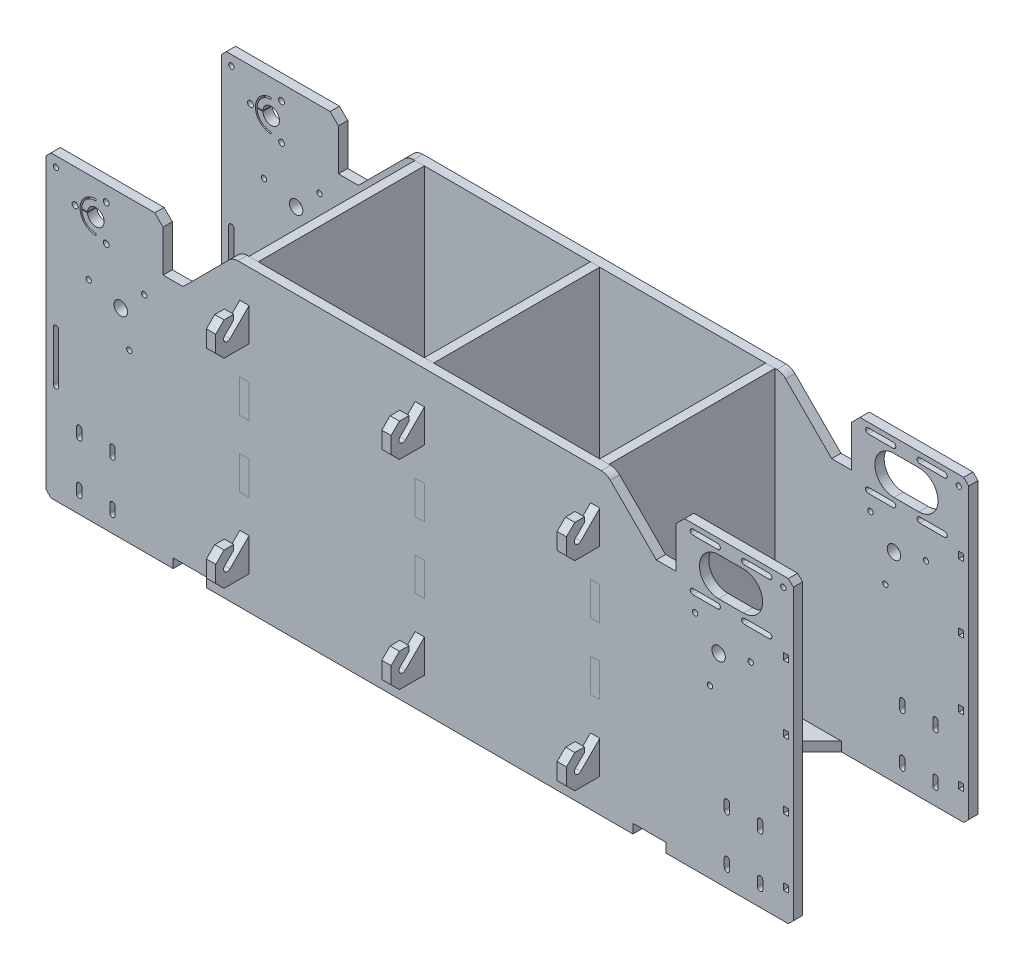
SolidWorks part; units mm, degrees
material "Perspex (TM) GS Acrylic Cast Sheet"
ref_plane "Front Plane" through (0, 0, 0) normal (0, 0, 1) x (1, 0, 0)
ref_plane "Top Plane" through (0, 0, 0) normal (0, 1, 0) x (1, 0, 0)
ref_plane "Right Plane" through (0, 0, 0) normal (1, 0, 0) x (0, 0, -1)
sketch "Sketch1" plane through (0, 0, 0) normal (0, 0, 1) x (1, 0, 0)
  line L0 (225, 180) -> (225, 0) construction
  line L1 (0, 0) -> (76.6, 0)
  line L2 (0, 0) -> (0, 180)
  line L4 (450, 0) -> (450, 180)
  line L5 (0, 90) -> (450, 90) construction
  line L6 (330.6, 180) -> (330.6, 0) construction
  line L7 (327.8, 160) -> (333.4, 160)
  line L8 (96.6, 0) -> (353.4, 0)
  line L12 (327.8, 160) -> (327.8, 140)
  line L13 (327.8, 140) -> (333.4, 140)
  line L14 (333.4, 160) -> (333.4, 140)
  line L15 (327.8, 120) -> (333.4, 120)
  line L16 (327.8, 120) -> (327.8, 100)
  line L17 (327.8, 100) -> (333.4, 100)
  line L18 (333.4, 120) -> (333.4, 100)
  line L19 (327.8, 80) -> (333.4, 80)
  line L20 (327.8, 80) -> (327.8, 60)
  line L21 (327.8, 60) -> (333.4, 60)
  line L22 (333.4, 80) -> (333.4, 60)
  line L23 (327.8, 40) -> (333.4, 40)
  line L24 (327.8, 40) -> (327.8, 20)
  line L25 (327.8, 20) -> (333.4, 20)
  line L26 (333.4, 40) -> (333.4, 20)
  line L27 (327.8, 40) -> (327.8, 20)
  line L28 (333.4, 40) -> (333.4, 20)
  line L29 (327.8, 80) -> (327.8, 60)
  line L30 (333.4, 80) -> (333.4, 60)
  line L31 (327.8, 120) -> (327.8, 100)
  line L32 (333.4, 120) -> (333.4, 100)
  line L33 (327.8, 160) -> (327.8, 140)
  line L34 (333.4, 160) -> (333.4, 140)
  line L39 (116.6, 160) -> (116.6, 140)
  line L40 (122.2, 160) -> (122.2, 140)
  line L41 (116.6, 120) -> (116.6, 100)
  line L42 (122.2, 120) -> (122.2, 100)
  line L43 (116.6, 80) -> (116.6, 60)
  line L44 (122.2, 80) -> (122.2, 60)
  line L45 (116.6, 40) -> (116.6, 20)
  line L46 (122.2, 40) -> (122.2, 20)
  line L47 (116.6, 40) -> (116.6, 20)
  line L48 (122.2, 20) -> (116.6, 20)
  line L49 (122.2, 40) -> (122.2, 20)
  line L50 (122.2, 40) -> (116.6, 40)
  line L51 (116.6, 80) -> (116.6, 60)
  line L52 (122.2, 60) -> (116.6, 60)
  line L53 (122.2, 80) -> (122.2, 60)
  line L54 (122.2, 80) -> (116.6, 80)
  line L55 (116.6, 120) -> (116.6, 100)
  line L56 (122.2, 100) -> (116.6, 100)
  line L57 (122.2, 120) -> (122.2, 100)
  line L58 (122.2, 120) -> (116.6, 120)
  line L59 (116.6, 160) -> (116.6, 140)
  line L60 (122.2, 140) -> (116.6, 140)
  line L61 (122.2, 160) -> (122.2, 140)
  line L66 (122.2, 160) -> (116.6, 160)
  line L67 (222.2, 160) -> (227.8, 160)
  line L72 (222.2, 160) -> (222.2, 140)
  line L73 (222.2, 140) -> (227.8, 140)
  line L74 (227.8, 160) -> (227.8, 140)
  line L75 (222.2, 120) -> (227.8, 120)
  line L76 (222.2, 120) -> (222.2, 100)
  line L77 (222.2, 100) -> (227.8, 100)
  line L78 (227.8, 120) -> (227.8, 100)
  line L79 (222.2, 80) -> (227.8, 80)
  line L80 (222.2, 80) -> (222.2, 60)
  line L81 (222.2, 60) -> (227.8, 60)
  line L82 (227.8, 80) -> (227.8, 60)
  line L83 (222.2, 40) -> (227.8, 40)
  line L84 (222.2, 40) -> (222.2, 20)
  line L85 (222.2, 20) -> (227.8, 20)
  line L86 (227.8, 40) -> (227.8, 20)
  line L88 (373.4, 0) -> (373.4, 5.6)
  line L89 (96.6, 0) -> (96.6, 5.6)
  line L90 (96.6, 5.6) -> (76.6, 5.6)
  line L91 (76.6, 0) -> (76.6, 5.6)
  line L92 (353.4, 5.6) -> (373.4, 5.6)
  line L93 (353.4, 0) -> (353.4, 5.6)
  line L94 (373.4, 0) -> (450, 0)
  line L95 (0, 180) -> (450, 180)
  point P1 (225, 160)
  point P2 (225, 120)
  point P9 (225, 80)
  point P11 (225, 40)
  point P12 (225, 180)
  dimension "D1" = 450
  dimension "D2" = 180
  dimension "D3" = 5.6
  dimension "D4" = 5.6
  dimension "D5" = 105.6
  dimension "D7" = 5.6
  dimension "D8" = 5.6
  dimension "D10" = 20
  dimension "D11" = 5.6
  dimension "D12" = 20
  dimension "D13" = 20
  dimension "D14" = 5.6
  dimension "D15" = 20
  dimension "D6" = 5.6
  dimension "D9" = 5.6
  dimension "D16" = 20
  dimension "D17" = 20
  dimension "D22" = 20
extrude "Boss-Extrude1" add sketch "Sketch1" along normal blind 5.6
ref_plane "Plane1" through (0, 0, 55.6) normal (0, 0, 1) x (1, 0, 0)
ref_plane "Plane2" through (225, 0, 0) normal (-1, 0, 0) x (0, 0, 1)
sketch "Sketch2" plane through (116.6, 0, 0) normal (1, 0, 0) x (0, 0, -1)
  line L0 (-56.3, 180) -> (-56.3, 0) construction
  line L1 (-5.6, 140) -> (0, 140)
  line L2 (0, 140) -> (0, 160)
  line L3 (-5.6, 0) -> (-25.6, 0)
  line L4 (0, 160) -> (-5.6, 160)
  line L5 (0, 160) -> (0, 140) construction
  line L7 (0, 120) -> (0, 100)
  line L9 (-5.6, 180) -> (-5.6, 160)
  line L10 (0, 80) -> (0, 60)
  line L11 (0, 120) -> (-5.6, 120)
  line L12 (-5.6, 140) -> (-5.6, 120)
  line L13 (0, 100) -> (-5.6, 100)
  line L14 (0, 40) -> (0, 20)
  line L15 (0, 80) -> (-5.6, 80)
  line L16 (-5.6, 100) -> (-5.6, 80)
  line L17 (0, 60) -> (-5.6, 60)
  line L18 (-45.6, 0) -> (-67, 0)
  line L19 (0, 40) -> (-5.6, 40)
  line L20 (-5.6, 60) -> (-5.6, 40)
  line L21 (0, 20) -> (-5.6, 20)
  line L22 (-5.6, 180) -> (-105.6, 180)
  line L23 (-105.6, 20) -> (-105.6, 0)
  line L24 (-5.6, 20) -> (-5.6, 0)
  line L27 (-131.2, 160) -> (-131.2, 140)
  line L28 (-131.2, 20) -> (-105.6, 20)
  line L29 (-105.6, 60) -> (-105.6, 40)
  line L30 (-131.2, 40) -> (-105.6, 40)
  line L31 (-111.2, 60) -> (-105.6, 60)
  line L32 (-105.6, 100) -> (-105.6, 80)
  line L33 (-111.2, 80) -> (-105.6, 80)
  line L34 (-111.2, 100) -> (-105.6, 100)
  line L35 (-105.6, 140) -> (-105.6, 120)
  line L36 (-111.2, 120) -> (-105.6, 120)
  line L37 (-111.2, 80) -> (-111.2, 60)
  line L38 (-105.6, 180) -> (-105.6, 160)
  line L39 (-131.2, 160) -> (-105.6, 160)
  line L40 (-111.2, 120) -> (-111.2, 100)
  line L42 (-131.2, 140) -> (-105.6, 140)
  line L44 (-131.2, 160) -> (-131.2, 140)
  line L45 (-111.2, 120) -> (-111.2, 100)
  line L46 (-111.2, 80) -> (-111.2, 60)
  line L47 (-131.2, 40) -> (-131.2, 20)
  line L48 (-67, 0) -> (-67, 5.6)
  line L49 (-87, 5.6) -> (-67, 5.6)
  line L50 (-25.6, 0) -> (-25.6, 5.6)
  line L51 (-25.6, 5.6) -> (-45.6, 5.6)
  line L52 (-45.6, 0) -> (-45.6, 5.6)
  line L53 (-87, 0) -> (-87, 5.6)
  line L54 (-87, 0) -> (-105.6, 0)
  dimension "D3" = 5.6
  dimension "D4" = 20
  dimension "D6" = 20
  dimension "D7" = 20
  dimension "D8" = 5.6
  dimension "D9" = 25.6
  dimension "D10" = 5.6
  dimension "D11" = 20
  dimension "D12" = 100
  dimension "D5" = 5
extrude "Boss-Extrude5" add sketch "Sketch2" along normal blind 5.6 separate body
chamfer "Chamfer1" distance 5 angle 45 4 edges at (119.4, 20, 131.2) (119.4, 40, 131.2) (119.4, 140, 131.2) (119.4, 160, 131.2)
sketch "Sketch3" plane through (116.6, 0, 0) normal (-1, 0, 0) x (0, 0, 1)
  line L0 (131.2, 155) -> (131.2, 145) construction
  line L1 (126.2, 160) -> (105.6, 160) construction
  line L2 (131.2, 35) -> (131.2, 25) construction
  line L3 (126.2, 40) -> (105.6, 40) construction
  line L4 (125.791, 151.591) -> (120.382, 157)
  line L5 (124.2, 150) -> (116.6269, 150) construction
  line L6 (122.609, 148.409) -> (111.018, 160)
  line L7 (120.382, 160) -> (120.382, 157)
  line L8 (111.018, 160) -> (120.382, 160)
  line L9 (125.791, 31.591) -> (120.382, 37)
  line L10 (122.609, 28.409) -> (111.018, 40)
  line L11 (124.75, 30) -> (117.9371, 30) construction
  line L12 (120.382, 37) -> (120.382, 40)
  line L13 (111.018, 40) -> (120.382, 40)
  arc A0 (122.609, 148.409) -> (125.791, 151.591) centre (124.2, 150) ccw
  arc A1 (122.609, 28.409) -> (125.791, 31.591) centre (124.2, 30) ccw
  dimension "D2" = 10
  dimension "D3" = 4.5
  dimension "D4" = 7
  dimension "D5" = 10
  dimension "D1" = 7
  dimension "D6" = 45
  dimension "D7" = 3
  dimension "D8" = 45
  dimension "D9" = 3
  dimension "D10" = 4.5
  dimension "D11" = 4.5
extrude "Cut-Extrude1" cut sketch "Sketch3" against normal blind 7
pattern_linear "LPattern2" count 3 spacing 105.6 along (1, 0, 0) of bodies 109 104
sketch "Sketch4" plane through (0, 0, 0) normal (0, -1, 0) x (1, 0, 0)
  line L0 (116.6, 5.6) -> (96.6, 5.6)
  line L2 (96.6, 5.6) -> (96.6, 0)
  line L3 (96.6, 0) -> (76.6, 0)
  line L4 (76.6, 0) -> (76.6, 5.6)
  line L5 (76.6, 5.6) -> (116.6, 45.6)
  line L6 (119.4, 25.6) -> (119.4, 45.6)
  line L8 (122.2, 25.6) -> (116.6, 25.6) construction
  line L10 (122.2, 45.6) -> (116.6, 45.6) construction
  line L11 (116.6, 5.6) -> (116.6, 25.6) construction
  line L12 (116.6, 25.6) -> (116.6, 5.6)
  line L13 (119.4, 45.6) -> (116.6, 45.6)
  line L14 (119.4, 25.6) -> (116.6, 25.6)
extrude "Boss-Extrude6" add sketch "Sketch4" against normal blind 5.6 separate body
mirror "Mirror3" about plane through (225, 0, 0) normal (-1, 0, 0) of bodies 110
sketch "Sketch5" plane through (0, 0, 0) normal (0, -1, 0) x (1, 0, 0)
  line L0 (122.2, 105.6) -> (122.2, 87)
  line L1 (122.2, 87) -> (119.4, 87)
  line L2 (122.2, 87) -> (116.6, 87) construction
  line L3 (119.4, 67) -> (122.2, 67)
  line L4 (122.2, 67) -> (122.2, 45.6)
  line L5 (122.2, 45.6) -> (119.4, 45.6)
  line L6 (119.4, 45.6) -> (119.4, 25.6)
  line L7 (119.4, 25.6) -> (122.2, 25.6)
  line L8 (122.2, 25.6) -> (116.6, 25.6) construction
  line L9 (122.2, 25.6) -> (122.2, 5.6)
  line L10 (122.2, 5.6) -> (222.2, 5.6)
  line L11 (222.2, 5.6) -> (222.2, 25.6)
  line L12 (222.2, 25.6) -> (225, 25.6)
  line L13 (227.8, 25.6) -> (222.2, 25.6) construction
  line L14 (225, 25.6) -> (225, 45.6)
  line L15 (227.8, 45.6) -> (222.2, 45.6) construction
  line L16 (225, 45.6) -> (222.2, 45.6)
  line L17 (222.2, 45.6) -> (222.2, 67)
  line L18 (222.2, 67) -> (225, 67)
  line L19 (227.8, 67) -> (222.2, 67) construction
  line L20 (225, 67) -> (225, 87)
  line L21 (227.8, 87) -> (222.2, 87) construction
  line L22 (225, 87) -> (222.2, 87)
  line L23 (222.2, 87) -> (222.2, 105.6)
  line L24 (222.2, 105.6) -> (122.2, 105.6)
  line L25 (119.4, 87) -> (119.4, 67)
  point P6 (119.4, 87)
extrude "Boss-Extrude7" add sketch "Sketch5" against normal blind 5.6 separate body
sketch "Sketch7" plane through (0, 0, 0) normal (0, -1, 0) x (1, 0, 0)
  line L0 (222.2, 105.6) -> (122.2, 105.6) construction
  line L1 (172.2, 78.6) -> (161.3747, 72.35) construction
  line L2 (172.2, 91.1) -> (172.2, 78.6) construction
  line L3 (222.2, 87) -> (222.2, 105.6) construction
  line L4 (222.2, 45.6) -> (222.2, 67) construction
  line L5 (172.2, 78.6) -> (183.0253, 72.35) construction
  line L6 (195.2, 68.1) -> (195.2, 55.6) construction
  line L7 (195.2, 55.6) -> (184.3747, 49.35) construction
  line L8 (195.2, 55.6) -> (206.0253, 49.35) construction
  line L9 (222.2, 45.6) -> (222.2, 67) construction
  circle A0 centre (195.2, 55.6) radius 12.5 construction
  circle A1 centre (195.2, 68.1) radius 1.6
  circle A2 centre (172.2, 91.1) radius 1.6
  circle A3 centre (183.0253, 72.35) radius 1.6
  circle A4 centre (172.2, 78.6) radius 12.5 construction
  circle A5 centre (195.2, 55.6) radius 4.1
  circle A6 centre (161.3747, 72.35) radius 1.6
  circle A7 centre (206.0253, 49.35) radius 1.6
  circle A8 centre (184.3747, 49.35) radius 1.6
  circle A9 centre (172.2, 78.6) radius 4.1
  circle A10 centre (172.2, 55.6) radius 6.5
  point P23 (172.2, 78.6)
  dimension "D1" = 25
  dimension "D2" = 3.2
  dimension "D4" = 25
  dimension "D5" = 3
  dimension "D3" = 8.2
  dimension "D6" = 27
  dimension "D7" = 27
  dimension "D8" = 50
  dimension "D9" = 50
  dimension "D10" = 120
  dimension "D12" = 3.2
  dimension "D13" = 3.2
  dimension "D14" = 12.5
  dimension "D15" = 12.5
  dimension "D18" = 50
  dimension "D19" = 50
  dimension "D20" = 13
  dimension "D11" = 120
  dimension "D16" = 120
  dimension "D17" = 120
extrude "Cut-Extrude3" cut sketch "Sketch7" against normal up to next (5.6 mm away)
pattern_linear "LPattern4" count 2 spacing 105.6 along (1, 0, 0) of bodies 123
sketch "Sketch8" plane through (0, 0, 5.6) normal (0, 0, 1) x (1, 0, 0)
  line L0 (435.5, 175.5) -> (420.5, 175.5) construction
  line L1 (435.5, 173.9) -> (420.5, 173.9)
  line L2 (435.5, 177.1) -> (420.5, 177.1)
  line L3 (404.5, 175.5) -> (389.5, 175.5) construction
  line L4 (404.5, 173.9) -> (389.5, 173.9)
  line L5 (404.5, 177.1) -> (389.5, 177.1)
  line L6 (404.5, 144.5) -> (389.5, 144.5) construction
  line L7 (404.5, 142.9) -> (389.5, 142.9)
  line L8 (404.5, 146.1) -> (389.5, 146.1)
  line L9 (435.5, 144.5) -> (420.5, 144.5) construction
  line L10 (435.5, 142.9) -> (420.5, 142.9)
  line L11 (435.5, 146.1) -> (420.5, 146.1)
  line L12 (435.5, 175.5) -> (404.5, 175.5) construction
  line L13 (420, 160) -> (405, 160) construction
  line L14 (420, 148.5) -> (405, 148.5)
  line L15 (420, 171.5) -> (405, 171.5)
  line L16 (0, 180) -> (450, 180) construction
  line L17 (450, 0) -> (450, 180) construction
  line L18 (0, 0) -> (0, 180) construction
  line L19 (30, 168.5) -> (30, 169.5)
  line L20 (30, 151.5) -> (30, 150.5)
  line L22 (25, 159.75) -> (21.5037, 159.75)
  line L23 (25, 160.25) -> (21.5037, 160.25)
  line L24 (20.5033, 160.25) -> (20.5, 160.25)
  line L25 (20.5033, 159.75) -> (20.5, 159.75)
  arc A0 (435.5, 173.9) -> (435.5, 177.1) centre (435.5, 175.5) ccw
  arc A1 (420.5, 177.1) -> (420.5, 173.9) centre (420.5, 175.5) ccw
  arc A2 (404.5, 173.9) -> (404.5, 177.1) centre (404.5, 175.5) ccw
  arc A3 (389.5, 177.1) -> (389.5, 173.9) centre (389.5, 175.5) ccw
  arc A4 (404.5, 142.9) -> (404.5, 146.1) centre (404.5, 144.5) ccw
  arc A5 (389.5, 146.1) -> (389.5, 142.9) centre (389.5, 144.5) ccw
  arc A6 (435.5, 142.9) -> (435.5, 146.1) centre (435.5, 144.5) ccw
  arc A7 (420.5, 146.1) -> (420.5, 142.9) centre (420.5, 144.5) ccw
  arc A8 (420, 148.5) -> (420, 171.5) centre (420, 160) ccw
  arc A9 (405, 171.5) -> (405, 148.5) centre (405, 160) ccw
  arc A10 (25.0062, 159.7501) -> (25.0062, 160.2499) centre (30, 160) ccw
  arc A11 (25, 159.75) -> (25.0062, 159.7501) centre (25, 160) ccw
  arc A12 (21.5037, 159.75) -> (30, 151.5) centre (30, 160) ccw
  arc A14 (30, 169.5) -> (30, 150.5) centre (30, 160) ccw
  arc A15 (30, 168.5) -> (21.5037, 160.25) centre (30, 160) ccw
  arc A19 (25.0062, 160.2499) -> (25, 160.25) centre (25, 160) ccw
  point P2 (428, 175.5)
  point P9 (412.5, 160)
  point P12 (397, 175.5)
  point P19 (397, 144.5)
  point P26 (428, 144.5)
  point P51 (22.75, 150)
  dimension "D2" = 1.6
  dimension "D9" = 15.5
  dimension "D11" = 30
  dimension "D12" = 30
  dimension "D13" = 20
  dimension "D14" = 10
  dimension "D16" = 3.5
  dimension "D17" = 1
  dimension "D1" = 15
  dimension "D5" = 31
  dimension "D6" = 15
  dimension "D7" = 23
  dimension "D8" = 15.5
  dimension "D10" = 20
  dimension "D15" = 0.5
  dimension "D3" = 2
  dimension "D4" = 2
extrude "Cut-Extrude4" cut sketch "Sketch8" against normal blind 10 contours L15 A9 L14 A8 | L11 A7 L10 A6 | L2 A1 L1 A0 | L5 A3 L4 A2 | A10 A19 L23 A15 L19 A14 L20 A12 L22 A11 | L7 A5 L8 A4
sketch "Sketch14" plane through (0, 0, 0) normal (0, 0, -1) x (-1, 0, 0)
  circle A0 centre (-30, 160) radius 12.5 construction
  circle A1 centre (-17.5, 160) radius 1.75
  arc A2 (-30, 150.5) -> (-30, 169.5) centre (-30, 160) ccw construction
  circle A3 centre (-36.25, 149.1747) radius 1.75
  circle A4 centre (-36.25, 170.8253) radius 1.75
  point P15 (-30, 160)
  dimension "D1" = 3.5
  dimension "D2" = 3
  dimension "D3" = 3
extrude "Cut-Extrude11" cut sketch "Sketch14" against normal up to next (5.6 mm away)
sketch "Sketch9" plane through (0, 0, 0) normal (0, 0, -1) x (-1, 0, 0)
  line L0 (-384.5, 180) -> (-335.2224, 180)
  line L1 (0, 180) -> (-450, 180) construction
  line L2 (-367.5, 150) -> (-379.5, 150)
  line L3 (-379.5, 150) -> (-379.5, 175)
  line L4 (-379.5, 175) -> (-384.5, 180)
  line L5 (-339.8383, 177.6617) -> (-367.5, 150)
  line L6 (-335.2224, 180) -> (-334.4608, 180)
  arc A0 (-339.8383, 177.6617) -> (-334.4608, 180) centre (-334.1814, 172.0049) cw
  arc A1 (-389.5, 173.9) -> (-389.5, 177.1) centre (-389.5, 175.5) ccw construction
  dimension "D5" = 8
  dimension "D6" = 10
  dimension "D1" = 12
  dimension "D2" = 45
  dimension "D3" = 45
  dimension "D4" = 25
extrude "Cut-Extrude5" cut sketch "Sketch9" against normal blind 10
mirror "Mirror4" about plane through (225, 0, 0) normal (-1, 0, 0) of "Cut-Extrude5"
sketch "Sketch10" plane through (0, 0, 0) normal (0, 0, -1) x (-1, 0, 0)
  line L0 (-405, 120) -> (-390.8579, 134.1421) construction
  circle A0 centre (-405, 120) radius 4.05
  circle A1 centre (-405, 120) radius 20 construction
  arc A2 (-405, 148.5) -> (-405, 171.5) centre (-405, 160) ccw construction
  circle A3 centre (-390.8579, 134.1421) radius 1.6
  circle A4 centre (-399.8236, 100.6815) radius 1.6
  circle A5 centre (-424.3185, 125.1764) radius 1.6
  point P16 (-405, 120)
  dimension "D1" = 0
  dimension "D2" = 0
  dimension "D3" = 8.1
  dimension "D4" = 3.2
  dimension "D6" = 40
  dimension "D5" = 3
extrude "Cut-Extrude6" cut sketch "Sketch10" against normal blind 10
sketch "Sketch11" plane through (0, 0, 5.6) normal (0, 0, 1) x (1, 0, 0)
  line L0 (450, 0) -> (450, 180) construction
  line L1 (447, 140) -> (444, 140)
  line L2 (447, 140) -> (447, 136)
  line L3 (447, 136) -> (444, 136)
  line L4 (444, 140) -> (444, 136)
  line L5 (384.5, 180) -> (450, 180) construction
  line L6 (444, 100) -> (444, 96)
  line L7 (447, 96) -> (444, 96)
  line L8 (447, 100) -> (447, 96)
  line L9 (447, 100) -> (444, 100)
  line L10 (444, 60) -> (444, 56)
  line L11 (447, 56) -> (444, 56)
  line L12 (447, 60) -> (447, 56)
  line L13 (447, 60) -> (444, 60)
  line L14 (444, 20) -> (444, 16)
  line L15 (447, 16) -> (444, 16)
  line L16 (447, 20) -> (447, 16)
  line L17 (447, 20) -> (444, 20)
  dimension "D1" = 3
  dimension "D2" = 3
  dimension "D3" = 4
  dimension "D4" = 40
  dimension "D5" = 4
extrude "Cut-Extrude7" cut sketch "Sketch11" against normal up to surface (5.6 mm away) up to face at (422.7185, 125.1764, 0)
sketch "Sketch12" plane through (0, 0, 5.6) normal (0, 0, 1) x (1, 0, 0)
  line L0 (384.5, 180) -> (450, 180) construction
  line L1 (450, 0) -> (450, 180) construction
  line L2 (6, 90) -> (6, 60) construction
  line L3 (7.6, 90) -> (7.6, 60)
  line L4 (4.4, 90) -> (4.4, 60)
  line L5 (0, 180) -> (65.5, 180) construction
  line L6 (0, 0) -> (0, 180) construction
  line L7 (0, 0) -> (76.6, 0) construction
  circle A0 centre (444, 174) radius 1.6
  circle A1 centre (6, 174) radius 1.6
  arc A2 (7.6, 90) -> (4.4, 90) centre (6, 90) ccw
  arc A3 (4.4, 60) -> (7.6, 60) centre (6, 60) ccw
  point P10 (6, 75)
  dimension "D1" = 3.2
  dimension "D2" = 6
  dimension "D3" = 6
  dimension "D4" = 3.2
  dimension "D5" = 6
  dimension "D6" = 6
  dimension "D7" = 1.6
  dimension "D8" = 30
  dimension "D9" = 60
extrude "Cut-Extrude8" cut sketch "Sketch12" against normal up to surface (5.6 mm away) up to face at (445.5, 18, 0)
chamfer "Chamfer2" distance 3 angle 45 2 edges at (0, 180, 2.8) (450, 180, 2.8)
chamfer "Chamfer3" distance 3 angle 45 2 edges at (450, 0, 2.8) (0, 0, 2.8)
sketch "Sketch13" plane through (0, 0, 0) normal (0, 0, -1) x (-1, 0, 0)
  line L2 (-225, 180) -> (-225, 0) construction
  line L3 (-115.5392, 180) -> (-334.4608, 180) construction
  line L4 (-96.6, 0) -> (-353.4, 0) construction
  line L5 (-430, 40) -> (-430, 45) construction
  line L6 (-431.6, 40) -> (-431.6, 45)
  line L7 (-428.4, 40) -> (-428.4, 45)
  line L8 (-450, 3) -> (-450, 177) construction
  line L10 (-410, 40) -> (-410, 45) construction
  line L11 (-411.6, 40) -> (-411.6, 45)
  line L12 (-408.4, 40) -> (-408.4, 45)
  line L13 (-410, 10) -> (-410, 15) construction
  line L14 (-411.6, 10) -> (-411.6, 15)
  line L15 (-408.4, 10) -> (-408.4, 15)
  line L16 (-430, 10) -> (-430, 15) construction
  line L17 (-431.6, 10) -> (-431.6, 15)
  line L18 (-428.4, 10) -> (-428.4, 15)
  line L19 (-20, 40) -> (-20, 45) construction
  line L20 (-18.4, 40) -> (-18.4, 45)
  line L21 (-21.6, 40) -> (-21.6, 45)
  line L22 (-40, 40) -> (-40, 45) construction
  line L23 (-38.4, 40) -> (-38.4, 45)
  line L24 (-41.6, 40) -> (-41.6, 45)
  line L25 (-40, 10) -> (-40, 15) construction
  line L26 (-38.4, 10) -> (-38.4, 15)
  line L27 (-41.6, 10) -> (-41.6, 15)
  line L28 (-20, 10) -> (-20, 15) construction
  line L29 (-18.4, 10) -> (-18.4, 15)
  line L30 (-21.6, 10) -> (-21.6, 15)
  arc A0 (-411.6, 40) -> (-408.4, 40) centre (-410, 40) ccw
  arc A2 (-408.4, 45) -> (-411.6, 45) centre (-410, 45) ccw
  arc A3 (-411.6, 10) -> (-408.4, 10) centre (-410, 10) ccw
  arc A4 (-408.4, 15) -> (-411.6, 15) centre (-410, 15) ccw
  arc A5 (-18.4, 40) -> (-21.6, 40) centre (-20, 40) cw
  arc A6 (-21.6, 45) -> (-18.4, 45) centre (-20, 45) cw
  arc A7 (-38.4, 40) -> (-41.6, 40) centre (-40, 40) cw
  arc A8 (-41.6, 45) -> (-38.4, 45) centre (-40, 45) cw
  arc A9 (-431.6, 40) -> (-428.4, 40) centre (-430, 40) ccw
  arc A10 (-428.4, 45) -> (-431.6, 45) centre (-430, 45) ccw
  arc A11 (-431.6, 10) -> (-428.4, 10) centre (-430, 10) ccw
  arc A12 (-428.4, 15) -> (-431.6, 15) centre (-430, 15) ccw
  arc A13 (-38.4, 10) -> (-41.6, 10) centre (-40, 10) cw
  arc A14 (-41.6, 15) -> (-38.4, 15) centre (-40, 15) cw
  arc A15 (-18.4, 10) -> (-21.6, 10) centre (-20, 10) cw
  arc A16 (-21.6, 15) -> (-18.4, 15) centre (-20, 15) cw
  point P5 (-20, 42.5)
  point P10 (-410, 42.5)
  point P24 (-40, 42.5)
  point P26 (-430, 42.5)
  point P34 (-410, 12.5)
  point P41 (-430, 12.5)
  point P52 (-40, 12.5)
  point P59 (-20, 12.5)
  dimension "D1" = 20
  dimension "D2" = 2
  dimension "D6" = 1.6
  dimension "D5" = 5
extrude "Cut-Extrude9" cut sketch "Sketch13" against normal up to surface (5.6 mm away) up to face at (6, 75, 5.6)
mirror "Mirror8" about plane through (225, 0, 0) normal (-1, 0, 0) of "Cut-Extrude6"
mirror "Mirror11" about plane through (0, 0, 55.6) normal (0, 0, 1) of bodies 134
other "Save Bodies1"
